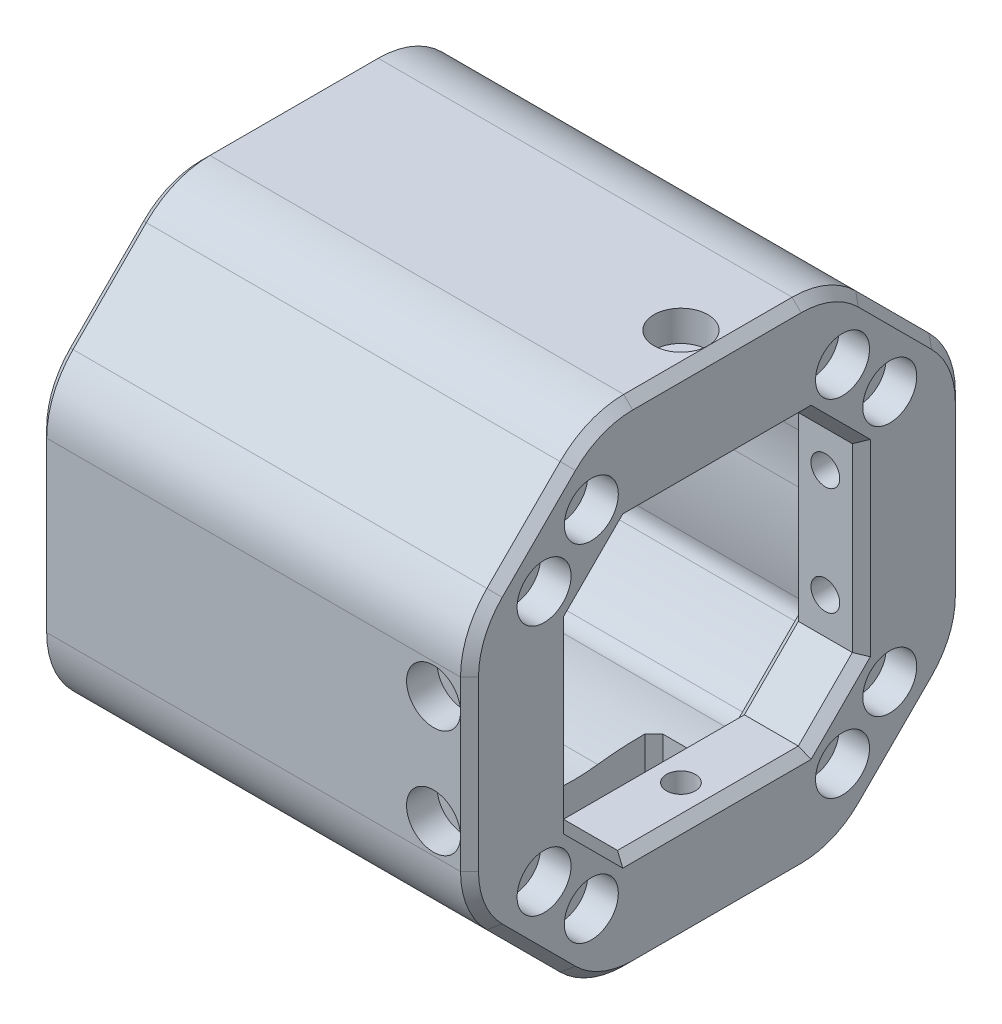
SolidWorks part; units mm, degrees
ref_plane "前视基准面" through (0, 0, 0) normal (0, 0, 1) x (1, 0, 0)
ref_plane "上视基准面" through (0, 0, 0) normal (0, 1, 0) x (1, 0, 0)
ref_plane "右视基准面" through (0, 0, 0) normal (1, 0, 0) x (0, 0, -1)
other "Configuration Table"
sketch "草图1" plane through (0, 0, 0) normal (1, 0, 0) x (0, 0, -1)
  line L1 (-27.5, -27.5) -> (27.5, -27.5)
  line L2 (-27.5, -27.5) -> (-27.5, 27.5)
  line L3 (-27.5, 27.5) -> (27.5, 27.5)
  line L4 (27.5, -27.5) -> (27.5, 27.5)
  line L5 (0, 27.5) -> (0, -27.5) construction
  line L6 (-27.5, 0) -> (27.5, 0) construction
  line L7 (-16.05, 16.05) -> (16.05, 16.05)
  line L8 (-16.05, 16.05) -> (-16.05, -16.05)
  line L9 (-16.05, -16.05) -> (16.05, -16.05)
  line L10 (16.05, 16.05) -> (16.05, -16.05)
  line L11 (0, -16.05) -> (0, 16.05) construction
  line L12 (-16.05, 0) -> (16.05, 0) construction
  circle A0 centre (0, 0) radius 31.25 construction
  circle A8 centre (0, 0) radius 18.05 construction
  dimension "D1" = 62.5
  dimension "D2" = 55
  dimension "D3" = 55
  dimension "D5" = 36.1
  dimension "D4" = 32.1
  dimension "D6" = 32.1
extrude "凸台-拉伸1" add sketch "草图1" along normal blind 8
sketch "草图2" plane through (8, 0, 0) normal (1, 0, 0) x (0, 0, -1)
  line L1 (0, 0) -> (13.9599, 19.2142) construction
  line L2 (0, 0) -> (23.75, 0) construction
  line L3 (0, 0) -> (0, 23.75) construction
  line L4 (0, 0) -> (19.2142, 13.9599) construction
  circle A1 centre (0, 0) radius 23.75 construction
  point P5 (13.9599, 19.2142)
  point P12 (19.2142, -13.9599)
  point P13 (-13.9599, -19.2142)
  point P14 (-19.2142, 13.9599)
  point P16 (19.2142, 13.9599)
  point P48 (13.9599, -19.2142)
  point P49 (-19.2142, -13.9599)
  point P50 (-13.9599, 19.2142)
  dimension "D1" = 47.5
  dimension "D2" = 4
  dimension "D3" = 4
  dimension "D4" = 36
  dimension "D6" = 36
chamfer "倒角1" distance 14 angle 45 4 edges at (4, -27.5, 27.5) (4, -27.5, -27.5) (4, 27.5, -27.5) (4, 27.5, 27.5)
chamfer "倒角2" distance 6 angle 45 4 edges at (4, -16.05, 16.05) (4, -16.05, -16.05) (4, 16.05, -16.05) (4, 16.05, 16.05)
sketch "草图3" plane through (0, 27.5, 0) normal (0, 1, 0) x (1, 0, 0)
  line L3 (8, 13.5) -> (8, -13.5) construction
  line L5 (0, 13.5) -> (0, -13.5) construction
  line L6 (0, 0) -> (4, 0) construction
  point P0 (4, 0)
  dimension "D2" = 4
sketch "草图4" plane through (0, 0, -27.5) normal (0, 0, -1) x (-1, 0, 0)
  line L0 (-4, 13.5) -> (-4, -13.5) construction
  line L1 (0, 13.5) -> (-8, 13.5) construction
  line L2 (-8, -13.5) -> (0, -13.5) construction
  line L3 (-8, 0) -> (0, 0) construction
  line L4 (-8, -13.5) -> (-8, 13.5) construction
  point P0 (-4, 6)
  point P1 (-4, -6)
  dimension "D1" = 6
  dimension "D2" = 6
hole_wizard "M3 六角圆柱头螺钉的柱形沉头孔1" positions "草图2" profile "草图5" counterbore size "M3" standard "GB" end condition through all
sketch "草图5" plane through (8, 19.2142, 13.9599) normal (0, 1, 0) x (0, 0, -1)
  line L0 (0, 0) -> (0, 8)
  line L1 (0, 8) -> (1.6, 8)
  line L3 (1.6, 8) -> (1.6, 3.4)
  line L4 (1.6, 3.4) -> (3, 3.4)
  line L5 (3, 3.4) -> (3, 0)
  line L7 (3, 0) -> (0, 0)
  line L11 (0, -6.35) -> (0, 107.95) construction
  dimension "通孔孔直径" = 3.2
  dimension "通孔孔深度" = 8
  dimension "柱形沉头孔直径" = 6
  dimension "柱形沉头孔深度" = 3.4
hole_wizard "M3 六角圆柱头螺钉的柱形沉头孔2" positions "草图3" profile "草图8" counterbore size "M3" standard "GB" end condition up to next
sketch "草图8" plane through (4, 27.5, 0) normal (1, 0, 0) x (0, 0, 1)
  line L0 (0, 0) -> (0, 11.45)
  line L1 (0, 11.45) -> (1.6, 11.45)
  line L3 (1.6, 11.45) -> (1.6, 3.4)
  line L4 (1.6, 3.4) -> (3, 3.4)
  line L5 (3, 3.4) -> (3, 0)
  line L7 (3, 0) -> (0, 0)
  line L11 (0, -6.35) -> (0, 107.95) construction
  dimension "通孔孔直径" = 3.2
  dimension "通孔孔深度" = 11.45
  dimension "柱形沉头孔直径" = 6
  dimension "柱形沉头孔深度" = 3.4
hole_wizard "M3 六角圆柱头螺钉的柱形沉头孔3" positions "草图4" profile "草图9" counterbore size "M3" standard "GB" end condition up to next
sketch "草图9" plane through (4, 6, -27.5) normal (1, 0, 0) x (0, 1, 0)
  line L0 (0, 0) -> (0, 11.45)
  line L1 (0, 11.45) -> (1.6, 11.45)
  line L3 (1.6, 11.45) -> (1.6, 3.4)
  line L4 (1.6, 3.4) -> (3, 3.4)
  line L5 (3, 3.4) -> (3, 0)
  line L7 (3, 0) -> (0, 0)
  line L11 (0, -6.35) -> (0, 107.95) construction
  dimension "通孔孔直径" = 3.2
  dimension "通孔孔深度" = 11.45
  dimension "柱形沉头孔直径" = 6
  dimension "柱形沉头孔深度" = 3.4
sketch "草图10" plane through (0, 0, 27.5) normal (0, 0, 1) x (1, 0, 0)
  line L0 (4, 13.5) -> (4, -13.5) construction
  line L1 (8, 13.5) -> (0, 13.5) construction
  line L2 (0, -13.5) -> (8, -13.5) construction
  point P6 (4, 6)
  point P7 (4, -6)
  dimension "D1" = 6
  dimension "D2" = 6
hole_wizard "M3 六角圆柱头螺钉的柱形沉头孔4" positions "草图10" profile "草图11" counterbore size "M3" standard "GB" end condition up to next
sketch "草图11" plane through (4, -6, 27.5) normal (1, 0, 0) x (0, -1, 0)
  line L0 (0, 0) -> (0, 11.45)
  line L1 (0, 11.45) -> (1.6, 11.45)
  line L3 (1.6, 11.45) -> (1.6, 3.4)
  line L4 (1.6, 3.4) -> (3, 3.4)
  line L5 (3, 3.4) -> (3, 0)
  line L7 (3, 0) -> (0, 0)
  line L11 (0, -6.35) -> (0, 107.95) construction
  dimension "通孔孔直径" = 3.2
  dimension "通孔孔深度" = 11.45
  dimension "柱形沉头孔直径" = 6
  dimension "柱形沉头孔深度" = 3.4
sketch "草图12" plane through (0, -27.5, 0) normal (0, -1, 0) x (1, 0, 0)
  line L0 (4, 13.5) -> (4, -13.5) construction
  line L1 (8, 13.5) -> (0, 13.5) construction
  line L2 (0, -13.5) -> (8, -13.5) construction
  point P6 (4, 0)
hole_wizard "M3 六角圆柱头螺钉的柱形沉头孔5" positions "草图12" profile "草图13" counterbore size "M3" standard "GB" end condition up to next
sketch "草图13" plane through (4, -27.5, 0) normal (1, 0, 0) x (0, 0, -1)
  line L0 (0, 0) -> (0, 11.45)
  line L1 (0, 11.45) -> (1.6, 11.45)
  line L3 (1.6, 11.45) -> (1.6, 3.4)
  line L4 (1.6, 3.4) -> (3, 3.4)
  line L5 (3, 3.4) -> (3, 0)
  line L7 (3, 0) -> (0, 0)
  line L11 (0, -6.35) -> (0, 107.95) construction
  dimension "通孔孔直径" = 3.2
  dimension "通孔孔深度" = 11.45
  dimension "柱形沉头孔直径" = 6
  dimension "柱形沉头孔深度" = 3.4
fillet "圆角1" radius 10 8 edges at (4, 27.5, 13.5) (4, 13.5, 27.5) (4, 27.5, -13.5) (4, 13.5, -27.5) (4, -13.5, -27.5) (4, -27.5, -13.5) (4, -27.5, 13.5) (4, -13.5, 27.5)
chamfer "倒角4" distance 1 angle 45 24 edges at (8, 0, -16.05) (8, -13.05, -13.05) (8, 13.05, -13.05) (8, 16.05, 0) (8, 13.05, 13.05) (8, -16.05, 0) (8, -13.05, 13.05) (8, 0, 16.05) (8, 0, -27.5) (8, 13.1847, -26.7388) (8, -13.1847, -26.7388) (8, 20.5, -20.5) (8, -20.5, -20.5) (8, 26.7388, -13.1847) (8, -26.7388, -13.1847) (8, 27.5, 0) (8, -27.5, 0) (8, 26.7388, 13.1847) (8, -26.7388, 13.1847) (8, 20.5, 20.5) (8, -20.5, 20.5) (8, 13.1847, 26.7388) (8, -13.1847, 26.7388) (8, 0, 27.5)
ref_plane "基准面2" through (0, 0, 0) normal (-1, 0, 0) x (0, 0, 1)
sketch "草图16" plane through (0, 0, 0) normal (-1, 0, 0) x (0, 0, 1)
  line L8 (0, 0) -> (-21.85, 0) construction
  line L9 (0, 0) -> (0, 21.85) construction
  line L10 (0, 0) -> (0, -21.85) construction
  line L11 (0, 21.75) -> (0, 0) construction
  line L12 (0, 0) -> (21.85, 0) construction
  line L15 (13.9599, 19.2142) -> (0, 0) construction
  line L16 (0, 0) -> (20.5, 20.5) construction
  line L17 (0, -21.75) -> (0, -21.85)
  line L19 (0, 21.75) -> (0, 21.85)
  line L20 (24.5711, 16.4289) -> (16.4289, 24.5711) construction
  line L29 (24.5711, 16.4289) -> (16.4289, 24.5711)
  line L30 (9.3579, 27.5) -> (-9.3579, 27.5)
  line L31 (-16.4289, 24.5711) -> (-24.5711, 16.4289)
  line L32 (-27.5, 9.3579) -> (-27.5, -9.3579)
  line L33 (-24.5711, -16.4289) -> (-16.4289, -24.5711)
  line L34 (-9.3579, -27.5) -> (9.3579, -27.5)
  line L35 (16.4289, -24.5711) -> (24.5711, -16.4289)
  line L36 (27.5, -9.3579) -> (27.5, 9.3579)
  line L37 (24.5711, 16.4289) -> (16.4289, 24.5711)
  line L38 (9.3579, 27.5) -> (-9.3579, 27.5)
  line L39 (-16.4289, 24.5711) -> (-24.5711, 16.4289)
  line L40 (-27.5, 9.3579) -> (-27.5, -9.3579)
  line L41 (-24.5711, -16.4289) -> (-16.4289, -24.5711)
  line L42 (-9.3579, -27.5) -> (9.3579, -27.5)
  line L43 (16.4289, -24.5711) -> (24.5711, -16.4289)
  line L44 (27.5, -9.3579) -> (27.5, 9.3579)
  arc A0 (15.4294, 21.2367) -> (13.5954, 21.6874) centre (13.9599, 19.2142) ccw construction
  arc A1 (2.7345, 21.5774) -> (13.5954, 21.6874) centre (7.7635, 61.26) ccw construction
  arc A2 (2.7345, 21.5774) -> (-2.7345, 21.5774) centre (0, 0) ccw construction
  arc A3 (21.2367, 15.4294) -> (15.4294, 21.2367) centre (0, 0) ccw construction
  arc A4 (21.2367, 15.4294) -> (21.6874, 13.5954) centre (19.2142, 13.9599) cw construction
  arc A5 (21.5774, 2.7345) -> (21.6874, 13.5954) centre (61.26, 7.7635) cw construction
  arc A6 (21.5774, 2.7345) -> (21.5774, -2.7345) centre (0, 0) cw construction
  arc A7 (21.5774, -2.7345) -> (21.6874, -13.5954) centre (61.26, -7.7635) ccw construction
  arc A8 (21.2367, -15.4294) -> (21.6874, -13.5954) centre (19.2142, -13.9599) ccw construction
  arc A9 (21.2367, -15.4294) -> (15.4294, -21.2367) centre (0, 0) cw construction
  arc A10 (15.4294, -21.2367) -> (13.5954, -21.6874) centre (13.9599, -19.2142) cw construction
  arc A11 (2.7345, -21.5774) -> (13.5954, -21.6874) centre (7.7635, -61.26) cw construction
  arc A12 (2.7345, -21.5774) -> (-2.7345, -21.5774) centre (0, 0) cw construction
  arc A13 (-15.4294, -21.2367) -> (-13.5954, -21.6874) centre (-13.9599, -19.2142) ccw construction
  arc A14 (-2.7345, -21.5774) -> (-13.5954, -21.6874) centre (-7.7635, -61.26) ccw construction
  arc A15 (-21.2367, -15.4294) -> (-15.4294, -21.2367) centre (0, 0) ccw construction
  arc A16 (-21.2367, -15.4294) -> (-21.6874, -13.5954) centre (-19.2142, -13.9599) cw construction
  arc A17 (-21.5774, -2.7345) -> (-21.6874, -13.5954) centre (-61.26, -7.7635) cw construction
  arc A18 (-21.5774, 2.7345) -> (-21.5774, -2.7345) centre (0, 0) ccw construction
  arc A19 (-21.5774, 2.7345) -> (-21.6874, 13.5954) centre (-61.26, 7.7635) ccw construction
  arc A20 (-21.2367, 15.4294) -> (-21.6874, 13.5954) centre (-19.2142, 13.9599) ccw construction
  arc A21 (-21.2367, 15.4294) -> (-15.4294, 21.2367) centre (0, 0) cw construction
  arc A22 (-15.4294, 21.2367) -> (-13.5954, 21.6874) centre (-13.9599, 19.2142) cw construction
  arc A23 (-2.7345, 21.5774) -> (-13.5954, 21.6874) centre (-7.7635, 61.26) cw construction
  arc A25 (-2.7345, 21.5774) -> (0, 21.75) centre (0, 0) cw construction
  arc A26 (-2.7345, -21.5774) -> (0, -21.75) centre (0, 0) ccw construction
  arc A28 (2.7471, -21.6766) -> (-2.7471, -21.6766) centre (0, 0) cw
  arc A29 (2.7471, -21.6766) -> (13.5808, -21.7864) centre (7.7635, -61.26) cw
  arc A30 (15.4881, -21.3176) -> (13.5808, -21.7864) centre (13.9599, -19.2142) cw
  arc A31 (21.3176, -15.4881) -> (15.4881, -21.3176) centre (0, 0) cw
  arc A32 (21.3176, -15.4881) -> (21.7864, -13.5808) centre (19.2142, -13.9599) ccw
  arc A33 (21.6766, -2.7471) -> (21.7864, -13.5808) centre (61.26, -7.7635) ccw
  arc A34 (21.6766, 2.7471) -> (21.6766, -2.7471) centre (0, 0) cw
  arc A35 (21.6766, 2.7471) -> (21.7864, 13.5808) centre (61.26, 7.7635) cw
  arc A36 (21.3176, 15.4881) -> (21.7864, 13.5808) centre (19.2142, 13.9599) cw
  arc A37 (21.3176, 15.4881) -> (15.4881, 21.3176) centre (0, 0) ccw
  arc A38 (15.4881, 21.3176) -> (13.5808, 21.7864) centre (13.9599, 19.2142) ccw
  arc A39 (2.7471, 21.6766) -> (13.5808, 21.7864) centre (7.7635, 61.26) ccw
  arc A40 (2.7471, 21.6766) -> (-2.7471, 21.6766) centre (0, 0) ccw
  arc A41 (-2.7471, 21.6766) -> (-13.5808, 21.7864) centre (-7.7635, 61.26) cw
  arc A42 (-15.4881, 21.3176) -> (-13.5808, 21.7864) centre (-13.9599, 19.2142) cw
  arc A43 (-21.3176, 15.4881) -> (-15.4881, 21.3176) centre (0, 0) cw
  arc A44 (-21.3176, 15.4881) -> (-21.7864, 13.5808) centre (-19.2142, 13.9599) ccw
  arc A45 (-21.6766, 2.7471) -> (-21.7864, 13.5808) centre (-61.26, 7.7635) ccw
  arc A46 (-21.6766, 2.7471) -> (-21.6766, -2.7471) centre (0, 0) ccw
  arc A47 (-21.6766, -2.7471) -> (-21.7864, -13.5808) centre (-61.26, -7.7635) cw
  arc A48 (-21.3176, -15.4881) -> (-21.7864, -13.5808) centre (-19.2142, -13.9599) cw
  arc A49 (-21.3176, -15.4881) -> (-15.4881, -21.3176) centre (0, 0) ccw
  arc A50 (-15.4881, -21.3176) -> (-13.5808, -21.7864) centre (-13.9599, -19.2142) ccw
  arc A51 (-2.7471, -21.6766) -> (-13.5808, -21.7864) centre (-7.7635, -61.26) ccw
  arc A52 (-2.7471, -21.6766) -> (0, -21.85) centre (0, 0) ccw
  arc A61 (16.4289, 24.5711) -> (9.3579, 27.5) centre (9.3579, 17.5) ccw
  arc A62 (-9.3579, 27.5) -> (-16.4289, 24.5711) centre (-9.3579, 17.5) ccw
  arc A63 (-24.5711, 16.4289) -> (-27.5, 9.3579) centre (-17.5, 9.3579) ccw
  arc A64 (-27.5, -9.3579) -> (-24.5711, -16.4289) centre (-17.5, -9.3579) ccw
  arc A65 (-16.4289, -24.5711) -> (-9.3579, -27.5) centre (-9.3579, -17.5) ccw
  arc A66 (9.3579, -27.5) -> (16.4289, -24.5711) centre (9.3579, -17.5) ccw
  arc A67 (24.5711, -16.4289) -> (27.5, -9.3579) centre (17.5, -9.3579) ccw
  arc A68 (27.5, 9.3579) -> (24.5711, 16.4289) centre (17.5, 9.3579) ccw
  arc A69 (16.4289, 24.5711) -> (9.3579, 27.5) centre (9.3579, 17.5) ccw
  arc A70 (-9.3579, 27.5) -> (-16.4289, 24.5711) centre (-9.3579, 17.5) ccw
  arc A71 (-24.5711, 16.4289) -> (-27.5, 9.3579) centre (-17.5, 9.3579) ccw
  arc A72 (-27.5, -9.3579) -> (-24.5711, -16.4289) centre (-17.5, -9.3579) ccw
  arc A73 (-16.4289, -24.5711) -> (-9.3579, -27.5) centre (-9.3579, -17.5) ccw
  arc A74 (9.3579, -27.5) -> (16.4289, -24.5711) centre (9.3579, -17.5) ccw
  arc A75 (24.5711, -16.4289) -> (27.5, -9.3579) centre (17.5, -9.3579) ccw
  arc A76 (27.5, 9.3579) -> (24.5711, 16.4289) centre (17.5, 9.3579) ccw
  dimension "D1" = 0
extrude "凸台-拉伸2" add sketch "草图16" along normal blind 40 contours L44 A76 L37 A69 L38 A70 L39 A71 L40 A72 L41 A73 L42 A74 L43 A75 A28 A51 A50 A49 A48 A47 A46 A45 A44 A43 A42 A41 A40 A39 A38 A37 A36 A35 A34 A33 A32 A31 A30 A29 region at (0, 12.887, 26.0202)
chamfer "倒角5" distance 1 angle 45 48 edges at (-40, -13.1847, 26.7388) (-40, -20.5, 20.5) (-40, -26.7388, 13.1847) (-40, -27.5, 0) (-40, -26.7388, -13.1847) (-40, -20.5, -20.5) (-40, -13.1847, -26.7388) (-40, 0, -27.5) (-40, 13.1847, -26.7388) (-40, 20.5, -20.5) (-40, 26.7388, -13.1847) (-40, 27.5, 0) (-40, 26.7388, 13.1847) (-40, 20.5, 20.5) (-40, 13.1847, 26.7388) (-40, 0, 27.5) (-40, -21.3621, 8.1677) (-40, -21.739, 14.5805) (-40, -18.6323, 18.6323) (-40, -14.5805, 21.739) (-40, -8.1677, 21.3621) (-40, 0, 21.85) (-40, 8.1677, 21.3621) (-40, 14.5805, 21.739) (-40, 18.6323, 18.6323) (-40, 21.739, 14.5805) (-40, 21.3621, 8.1677) (-40, 21.85, 0) (-40, 21.3621, -8.1677) (-40, 21.739, -14.5805) (-40, 18.6323, -18.6323) (-40, 14.5805, -21.739) (-40, 8.1677, -21.3621) (-40, 0, -21.85) (-40, -8.1677, -21.3621) (-40, -14.5805, -21.739) (-40, -18.6323, -18.6323) (-40, -21.739, -14.5805) (-40, -21.3621, -8.1677) (-40, -21.85, 0) (0, 13.05, 13.05) (0, 16.05, 0) (0, 13.05, -13.05) (0, 0, -16.05) (0, -13.05, -13.05) (0, -16.05, 0) (0, -13.05, 13.05) (0, 0, 16.05)
sketch "草图18" plane through (0, -27.5, 0) normal (0, -1, 0) x (1, 0, 0)
  line L0 (-39, 0) -> (-8, 0)
  line L1 (-39, 9.3579) -> (-39, -9.3579) construction
  line L2 (8, 9.3579) -> (8, -9.3579) construction
  line L3 (-8, 9) -> (0, 9)
  line L4 (-8, 9) -> (-8, -9)
  line L5 (-8, -9) -> (0, -9)
  line L6 (0, 9) -> (0, -9)
  point P9 (-8, 0)
  dimension "D1" = 8
  dimension "D2" = 18
  dimension "D3" = 8
extrude "切除-拉伸1" cut sketch "草图18" against normal blind 40 contours L6 L3 L4 L5 region at (-4, -27.5, 0)
chamfer "倒角6" distance 1 angle 45 4 edges at (-8, -24.4396, -9) (0, -24.4396, -9) (-8, -24.4396, 9) (0, -24.4396, 9)
chamfer "倒角7" distance 1 angle 45 8 edges at (-7.5, -27.5, 8.5) (-8, -27.5, 0) (-7.5, -27.5, -8.5) (-4, -27.5, -9) (-0.5, -27.5, -8.5) (0, -27.5, 0) (-0.5, -27.5, 8.5) (-4, -27.5, 9)
